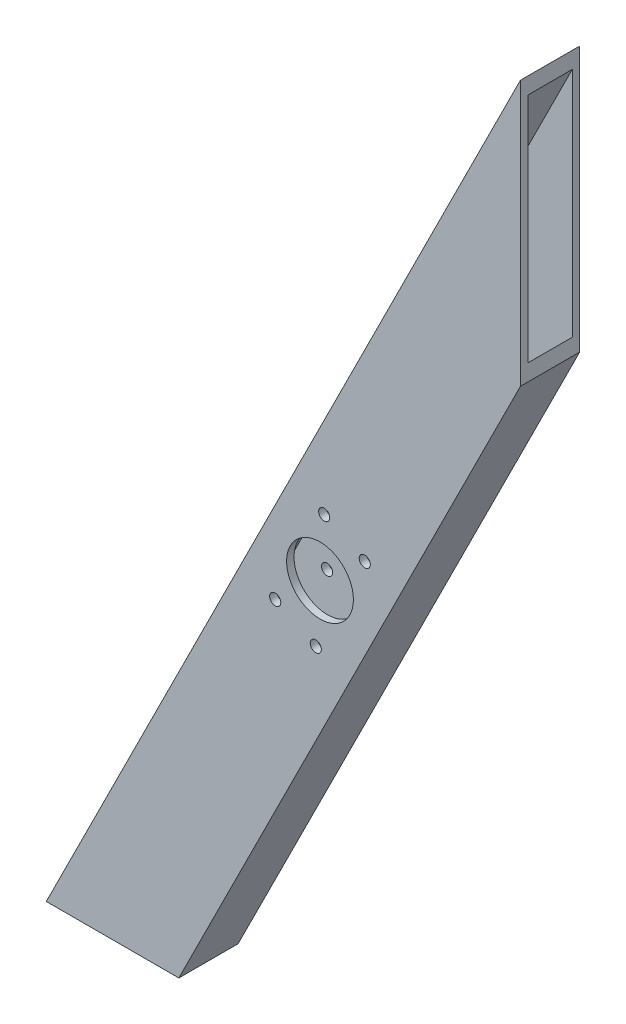
SolidWorks part; units mm, degrees
material "6063-T1"
ref_plane "Front Plane" through (0, 0, 0) normal (0, 0, 1) x (1, 0, 0)
ref_plane "Top Plane" through (0, 0, 0) normal (0, 1, 0) x (1, 0, 0)
ref_plane "Right Plane" through (0, 0, 0) normal (1, 0, 0) x (0, 0, -1)
sketch "Sketch1" plane through (0, 0, 0) normal (0, 0, 1) x (1, 0, 0)
  line L0 (0, 0) -> (203.2, 406.4)
  line L1 (203.2, 406.4) -> (203.2, 292.8077)
  line L2 (203.2, 292.8077) -> (56.7961, 0)
  line L3 (56.7961, 0) -> (0, 0)
  dimension "D1" = 203.2
  dimension "D2" = 406.4
  dimension "D3" = 50.8
extrude "Boss-Extrude1" add sketch "Sketch1" along normal blind 25.4
shell "Shell1" thickness 3.175 removed face at (203.2, 349.6039, 12.7) removed face at (28.3981, 0, 12.7)
sketch "Sketch2" plane through (0, 0, 25.4) normal (0, 0, 1) x (1, 0, 0)
  line L0 (56.7961, 0) -> (203.2, 292.8077) construction
  line L1 (3.5498, 0) -> (53.2464, 0) construction
  circle A0 centre (117.2981, 177.8) radius 14.3129
  dimension "D2" = 28.6258
  dimension "D1" = 25.4
  dimension "D3" = 177.8
extrude "Cut-Extrude1" cut sketch "Sketch2" against normal through all
sketch "Sketch3" plane through (0, 0, 25.4) normal (0, 0, 1) x (1, 0, 0)
  line L0 (136.4866, 194.4421) -> (105.0742, 210.1483) construction
  line L1 (203.2, 406.4) -> (0, 0) construction
  circle A0 centre (117.2981, 177.8) radius 25.4 construction
  circle A1 centre (136.4866, 194.4421) radius 2.3813
  circle A2 centre (142.6342, 175.9994) radius 2.3812
  circle A3 centre (133.9402, 158.6115) radius 2.3813
  circle A4 centre (115.4975, 152.4639) radius 2.3813
  circle A5 centre (98.1095, 161.1579) radius 2.3813
  circle A6 centre (91.962, 179.6006) radius 2.3813
  circle A7 centre (100.6559, 196.9885) radius 2.3813
  circle A8 centre (119.0986, 203.1361) radius 2.3813
  point P22 (117.2981, 177.8)
  dimension "D1" = 50.8
  dimension "D2" = 4.7625
  dimension "D3" = 8
extrude "Cut-Extrude2" cut sketch "Sketch3" against normal through all contours A8 | A1 | A5 | A4 region at (136.4866, 194.4421, 25.4) region at (115.4975, 152.4639, 25.4) region at (98.1095, 161.1579, 25.4) region at (119.0986, 203.1361, 25.4)
